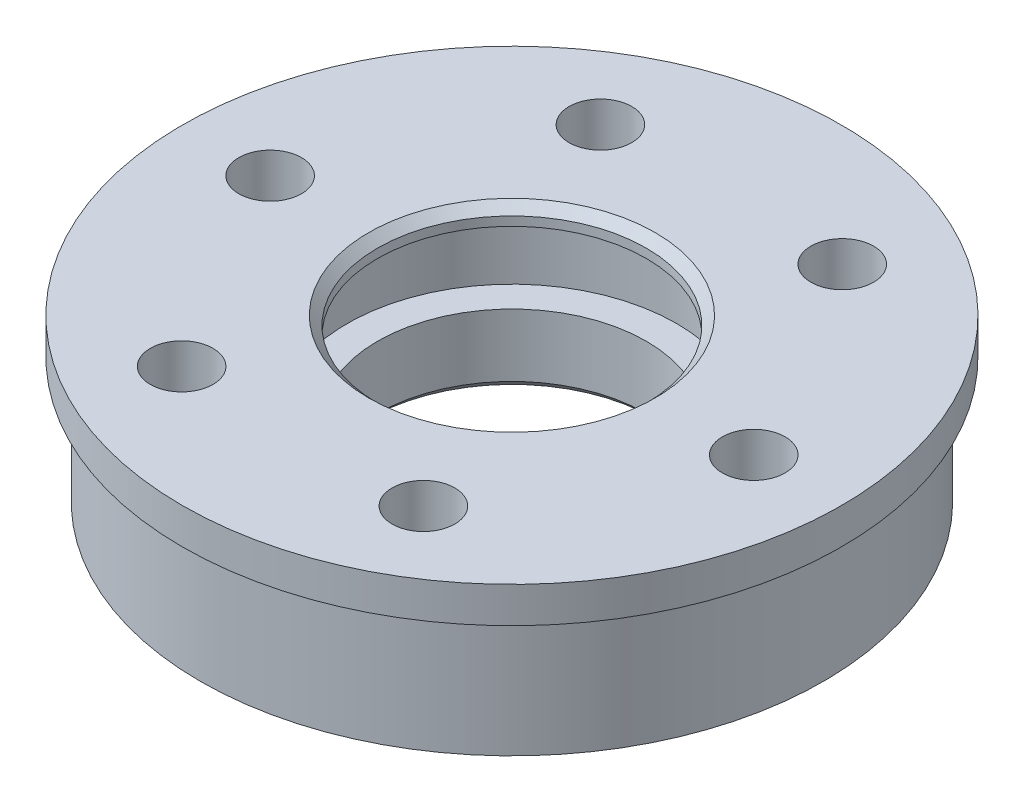
SolidWorks part; units mm, degrees
ref_plane "Front Plane" through (0, 0, 0) normal (0, 0, 1) x (1, 0, 0)
ref_plane "Top Plane" through (0, 0, 0) normal (0, 1, 0) x (1, 0, 0)
ref_plane "Right Plane" through (0, 0, 0) normal (1, 0, 0) x (0, 0, -1)
sketch "Sketch1" plane through (0, 0, 0) normal (0, 1, 0) x (1, 0, 0)
  circle A0 centre (0, 0) radius 13.5 construction
  circle A1 centre (13.5, 0) radius 1.75
  circle A2 centre (6.75, -11.6913) radius 1.75
  circle A3 centre (-6.75, -11.6913) radius 1.75
  circle A4 centre (-13.5, 0) radius 1.75
  circle A5 centre (-6.75, 11.6913) radius 1.75
  circle A6 centre (6.75, 11.6913) radius 1.75
  circle A7 centre (0, 0) radius 17.4
  circle A8 centre (0, 0) radius 7.5
  point P17 (0, 0)
  dimension "D1" = 27
  dimension "D2" = 3.5
  dimension "D4" = 34.8
  dimension "D5" = 15
  dimension "D3" = 6
extrude "Boss-Extrude1" add sketch "Sketch1" along normal mid plane 9
sketch "Sketch2" plane through (0, 0, 0) normal (0, 1, 0) x (1, 0, 0)
  circle A0 centre (0, 0) radius 9.2
  dimension "D1" = 18.4
extrude "Cut-Extrude1" cut sketch "Sketch2" along normal blind 4 from offset 0.5 offset against normal yes
sketch "Sketch3" plane through (0, -4.5, 0) normal (0, -1, 0) x (1, 0, 0)
  circle A0 centre (0, 0) radius 11.75
  circle A1 centre (0, 0) radius 15.25
  circle A2 centre (-13.5, 0) radius 1.75 construction
extrude "Boss-Extrude2" add sketch "Sketch3" against normal blind 1.5
chamfer "Chamfer1" distance 0.5 angle 45 2 edges at (0, -4.5, 7.5) (0, 4.5, 7.5)
sketch "Sketch4" plane through (0, 4.5, 0) normal (0, 1, 0) x (1, 0, 0)
  circle A0 centre (0, 0) radius 18.4
  circle A1 centre (0, 0) radius 17.4 construction
  circle A2 centre (0, 0) radius 17.4
  dimension "D1" = 1
extrude "Boss-Extrude3" add sketch "Sketch4" against normal blind 2
sketch "Sketch5" plane through (0, -4.5, 0) normal (0, -1, 0) x (-1, 0, 0)
  line L0 (0, 0) -> (-10.8253, -6.25) construction
  line L1 (0, 0) -> (-12.5, 0) construction
  circle A0 centre (0, 0) radius 12.5 construction
  circle A1 centre (-10.8253, -6.25) radius 2.35
  circle A2 centre (-10.8253, 6.25) radius 2.35
  circle A3 centre (0, 12.5) radius 2.35
  circle A4 centre (10.8253, 6.25) radius 2.35
  circle A5 centre (10.8253, -6.25) radius 2.35
  circle A6 centre (0, -12.5) radius 2.35
  point P18 (0, 0)
  dimension "D1" = 4.7
  dimension "D2" = 25
  dimension "D3" = 30
  dimension "D4" = 6
extrude "Cut-Extrude2" cut sketch "Sketch5" against normal blind 4
chamfer "Chamfer2" [suppressed] distance 3 angle 45
equation "\"D5@Sketch1\"=18-3"
